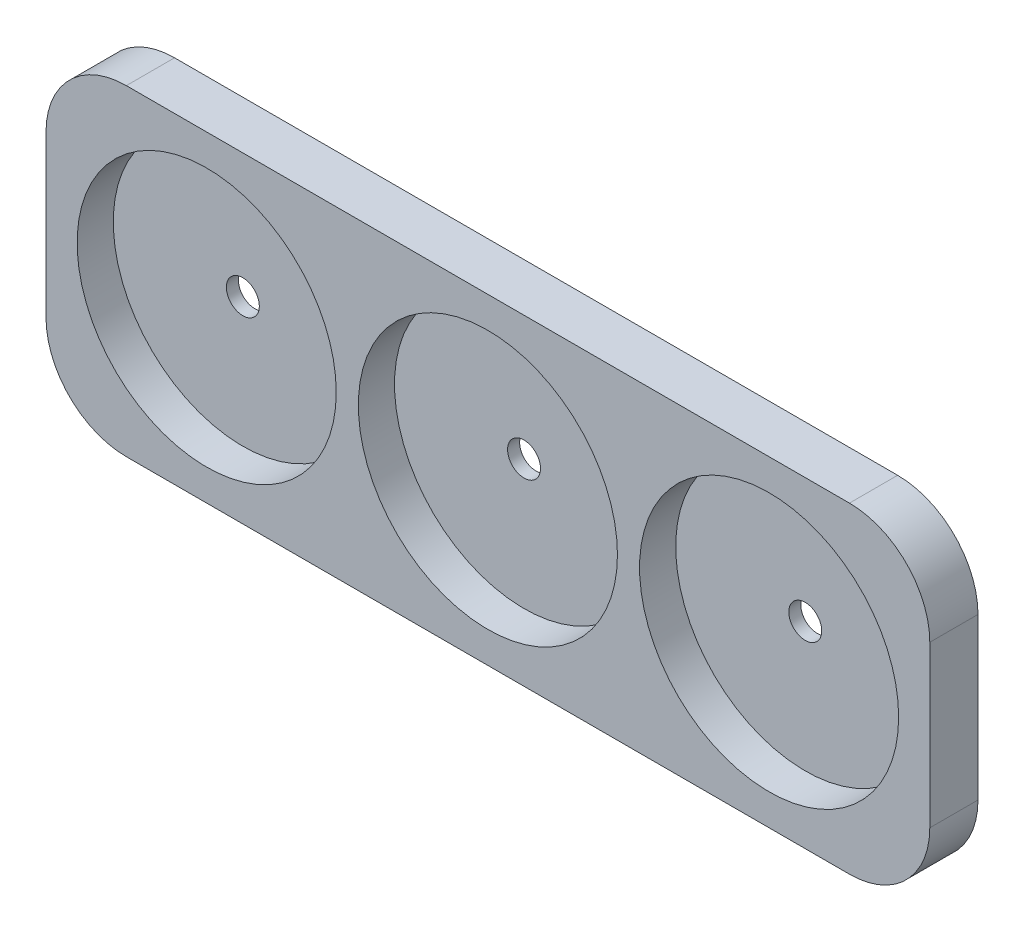
SolidWorks part; units mm, degrees
ref_plane "Front Plane" through (0, 0, 0) normal (0, 0, 1) x (1, 0, 0)
ref_plane "Top Plane" through (0, 0, 0) normal (0, 1, 0) x (1, 0, 0)
ref_plane "Right Plane" through (0, 0, 0) normal (1, 0, 0) x (0, 0, -1)
sketch "Sketch1" plane through (0, 0, 0) normal (0, 0, 1) x (1, 0, 0)
  line L1 (-55, 20) -> (55, 20)
  line L2 (-55, 20) -> (-55, -20)
  line L3 (-55, -20) -> (55, -20)
  line L4 (55, 20) -> (55, -20)
  line L5 (-55, 20) -> (55, -20) construction
  line L6 (-55, -20) -> (55, 20) construction
  point P0 (0, 0)
  dimension "D1" = 40
  dimension "D2" = 110
extrude "Boss-Extrude1" add sketch "Sketch1" along normal blind 6
sketch "Sketch2" plane through (0, 0, 6) normal (0, 0, 1) x (1, 0, 0)
  circle A0 centre (0, 0) radius 16.125
  circle A1 centre (35, 0) radius 16.125
  circle A2 centre (-35, 0) radius 16.125
  point P7 (0, 0)
  dimension "D1" = 32.25
  dimension "D2" = 70
  dimension "D3" = 35
extrude "Cut-Extrude1" cut sketch "Sketch2" against normal blind 4.5
fillet "Fillet1" radius 10 4 edges at (55, -20, 3) (55, 20, 3) (-55, 20, 3) (-55, -20, 3)
sketch "Sketch3" plane through (0, 0, 1.5) normal (0, 0, 1) x (1, 0, 0)
  circle A0 centre (0, 0) radius 2.05
  circle A1 centre (35, 0) radius 2.05
  circle A2 centre (-35, 0) radius 2.05
  dimension "D1" = 4.1
extrude "Cut-Extrude2" cut sketch "Sketch3" against normal through all
